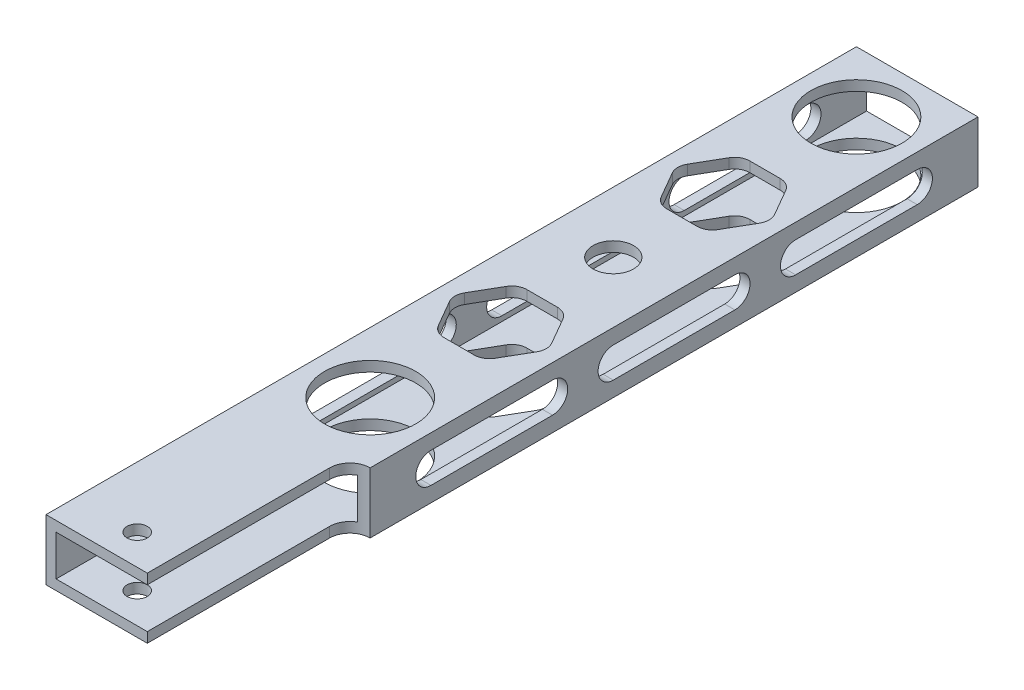
SolidWorks part; units mm, degrees
material "6063-T6"
ref_plane "Front" through (0, 0, 0) normal (0, 0, 1) x (1, 0, 0)
ref_plane "Top" through (0, 0, 0) normal (0, 1, 0) x (1, 0, 0)
ref_plane "Right" through (0, 0, 0) normal (1, 0, 0) x (0, 0, -1)
sketch "Sketch1" plane through (0, 0, 0) normal (0, 0, 1) x (1, 0, 0)
  line L0 (3.175, 3.175) -> (34.925, 3.175)
  line L1 (0, 0) -> (38.1, 0)
  line L2 (0, 0) -> (0, 19.05)
  line L3 (0, 19.05) -> (38.1, 19.05)
  line L4 (38.1, 0) -> (38.1, 19.05)
  line L5 (34.925, 3.175) -> (34.925, 15.875)
  line L6 (3.175, 15.875) -> (34.925, 15.875)
  line L7 (3.175, 3.175) -> (3.175, 15.875)
  dimension "D1" = 19.05
  dimension "D2" = 38.1
  dimension "D3" = 3.175
extrude "Boss-Extrude1" add sketch "Sketch1" along normal blind 254
sketch "Sketch2" plane through (0, 19.05, 0) normal (0, 1, 0) x (1, 0, 0)
  line L0 (19.05, 0) -> (19.05, -19.05) construction
  line L2 (19.05, -19.05) -> (19.05, -171.45) construction
  line L4 (38.1, -254) -> (38.1, 0) construction
  line L5 (38.1, 0) -> (0, 0) construction
  circle A0 centre (19.05, -19.05) radius 14.2875
  circle A1 centre (19.05, -171.45) radius 14.2875
  dimension "D1" = 28.575
  dimension "D4" = 28.575
  dimension "D2" = 19.05
  dimension "D3" = 152.4
  dimension "D5" = 19.05
extrude "Cut-Extrude1" cut sketch "Sketch2" against normal through all
sketch "Sketch3" plane through (0, 19.05, 0) normal (0, 1, 0) x (1, 0, 0)
  line L0 (19.05, -244.475) -> (19.05, -254) construction
  line L1 (38.1, -254) -> (0, -254) construction
  circle A0 centre (19.05, -244.475) radius 3.175
  dimension "D1" = 6.35
  dimension "D2" = 9.525
extrude "Cut-Extrude2" cut sketch "Sketch3" against normal through all
sketch "Sketch4" plane through (0, 19.05, 0) normal (0, 1, 0) x (1, 0, 0)
  line L0 (31.75, -254) -> (31.75, -196.85)
  line L1 (38.1, -254) -> (0, -254) construction
  line L2 (38.1, -190.5) -> (38.1, -254)
  line L3 (38.1, -254) -> (38.1, 0) construction
  line L4 (38.1, -254) -> (31.75, -254)
  arc A0 (38.1, -190.5) -> (31.75, -196.85) centre (38.1, -196.85) ccw
  dimension "D1" = 6.35
  dimension "D2" = 57.15
extrude "Cut-Extrude3" cut sketch "Sketch4" against normal through all
sketch "Sketch5" plane through (0, 0, 0) normal (0, -1, 0) x (1, 0, 0)
  circle A0 centre (19.05, 95.25) radius 2.667 construction
  circle A1 centre (19.05, 95.25) radius 2.667
extrude "Cut-Extrude4" cut sketch "Sketch5" against normal through all
sketch "Sketch6" plane through (0, 19.05, 0) normal (0, 1, 0) x (1, 0, 0)
  circle A0 centre (19.05, -95.25) radius 6.35
  circle A1 centre (19.05, -95.25) radius 2.667 construction
  dimension "D1" = 12.7
sketch "Sketch7" plane through (0, 0, 0) normal (-1, 0, 0) x (0, 0, 1)
  line L0 (19.05, 9.525) -> (57.15, 9.525) construction
  line L1 (19.05, 14.2875) -> (57.15, 14.2875)
  line L2 (19.05, 4.7625) -> (57.15, 4.7625)
  line L3 (34.9537, 14.2875) -> (34.9537, 19.05) construction
  line L4 (254, 19.05) -> (0, 19.05) construction
  line L5 (40.4377, 4.7625) -> (40.4377, 0) construction
  line L6 (254, 0) -> (0, 0) construction
  line L7 (0, 19.05) -> (0, 0) construction
  line L8 (92.1037, 14.2875) -> (92.1037, 19.05) construction
  line L9 (97.5877, 4.7625) -> (97.5877, 0) construction
  line L10 (76.2, 9.525) -> (114.3, 9.525) construction
  line L11 (76.2, 14.2875) -> (114.3, 14.2875)
  line L12 (76.2, 4.7625) -> (114.3, 4.7625)
  line L13 (149.2537, 14.2875) -> (149.2537, 19.05) construction
  line L14 (154.7377, 4.7625) -> (154.7377, 0) construction
  line L15 (133.35, 9.525) -> (171.45, 9.525) construction
  line L18 (133.35, 14.2875) -> (171.45, 14.2875)
  line L19 (133.35, 4.7625) -> (171.45, 4.7625)
  line L20 (196.85, 9.525) -> (234.95, 9.525) construction
  line L22 (196.85, 14.2875) -> (234.95, 14.2875)
  line L23 (196.85, 4.7625) -> (234.95, 4.7625)
  arc A0 (19.05, 14.2875) -> (19.05, 4.7625) centre (19.05, 9.525) ccw
  arc A1 (57.15, 4.7625) -> (57.15, 14.2875) centre (57.15, 9.525) ccw
  arc A2 (76.2, 14.2875) -> (76.2, 4.7625) centre (76.2, 9.525) ccw
  arc A3 (114.3, 4.7625) -> (114.3, 14.2875) centre (114.3, 9.525) ccw
  arc A6 (133.35, 14.2875) -> (133.35, 4.7625) centre (133.35, 9.525) ccw
  arc A7 (171.45, 4.7625) -> (171.45, 14.2875) centre (171.45, 9.525) ccw
  arc A8 (196.85, 14.2875) -> (196.85, 4.7625) centre (196.85, 9.525) ccw
  arc A9 (234.95, 4.7625) -> (234.95, 14.2875) centre (234.95, 9.525) ccw
  point P2 (38.1, 9.525)
  point P20 (95.25, 9.525)
  point P30 (152.4, 9.525)
  point P43 (215.9, 9.525)
  dimension "D1" = 9.525
  dimension "D2" = 38.1
  dimension "D3" = 19.05
  dimension "D5" = 19.05
  dimension "D6" = 25.4
  dimension "D7" = 38.1
  dimension "D4" = 3
extrude "Cut-Extrude6" cut sketch "Sketch7" against normal through all
sketch "Sketch8" plane through (0, 19.05, 0) normal (0, 1, 0) x (1, 0, 0)
  line L0 (19.05, -60.7208) -> (38.1, -60.7208) construction
  line L1 (5.4006, -63.102) -> (10.1631, -71.3509)
  line L2 (14.2875, -73.7322) -> (23.8125, -73.7322)
  line L3 (27.9369, -71.3509) -> (32.6994, -63.102)
  line L4 (32.6994, -58.3395) -> (27.9369, -50.0906)
  line L5 (23.8125, -47.7094) -> (14.2875, -47.7094)
  line L6 (10.1631, -50.0906) -> (5.4006, -58.3395)
  line L7 (38.1, -190.5) -> (38.1, 0) construction
  line L8 (5.4006, -132.952) -> (10.1631, -141.2009)
  line L9 (14.2875, -143.5822) -> (23.8125, -143.5822)
  line L10 (27.9369, -141.2009) -> (32.6994, -132.952)
  line L11 (32.6994, -128.1895) -> (27.9369, -119.9406)
  line L12 (23.8125, -117.5594) -> (14.2875, -117.5594)
  line L13 (10.1631, -119.9406) -> (5.4006, -128.1895)
  line L14 (19.05, -130.5708) -> (38.1, -130.5708) construction
  line L15 (0, -254) -> (0, 0) construction
  arc A0 (23.8125, -73.7322) -> (27.9369, -71.3509) centre (23.8125, -68.9697) ccw
  arc A1 (10.1631, -71.3509) -> (14.2875, -73.7322) centre (14.2875, -68.9697) ccw
  arc A2 (5.4006, -63.102) -> (5.4006, -58.3395) centre (9.525, -60.7208) cw
  arc A3 (14.2875, -47.7094) -> (10.1631, -50.0906) centre (14.2875, -52.4719) ccw
  arc A4 (27.9369, -50.0906) -> (23.8125, -47.7094) centre (23.8125, -52.4719) ccw
  arc A5 (32.6994, -63.102) -> (32.6994, -58.3395) centre (28.575, -60.7208) ccw
  arc A6 (23.8125, -143.5822) -> (27.9369, -141.2009) centre (23.8125, -138.8197) ccw
  arc A7 (10.1631, -141.2009) -> (14.2875, -143.5822) centre (14.2875, -138.8197) ccw
  arc A8 (5.4006, -132.952) -> (5.4006, -128.1895) centre (9.525, -130.5708) cw
  arc A9 (14.2875, -117.5594) -> (10.1631, -119.9406) centre (14.2875, -122.3219) ccw
  arc A10 (27.9369, -119.9406) -> (23.8125, -117.5594) centre (23.8125, -122.3219) ccw
  arc A11 (32.6994, -132.952) -> (32.6994, -128.1895) centre (28.575, -130.5708) ccw
  point P22 (34.0743, -60.7208)
  dimension "D1" = 4.7625
  dimension "D3" = 19.05
  dimension "D4" = 9.525
  dimension "D2" = 2
extrude "Cut-Extrude7" cut sketch "Sketch8" against normal through all
extrude "Cut-Extrude8" cut sketch "Sketch6" against normal up to next
